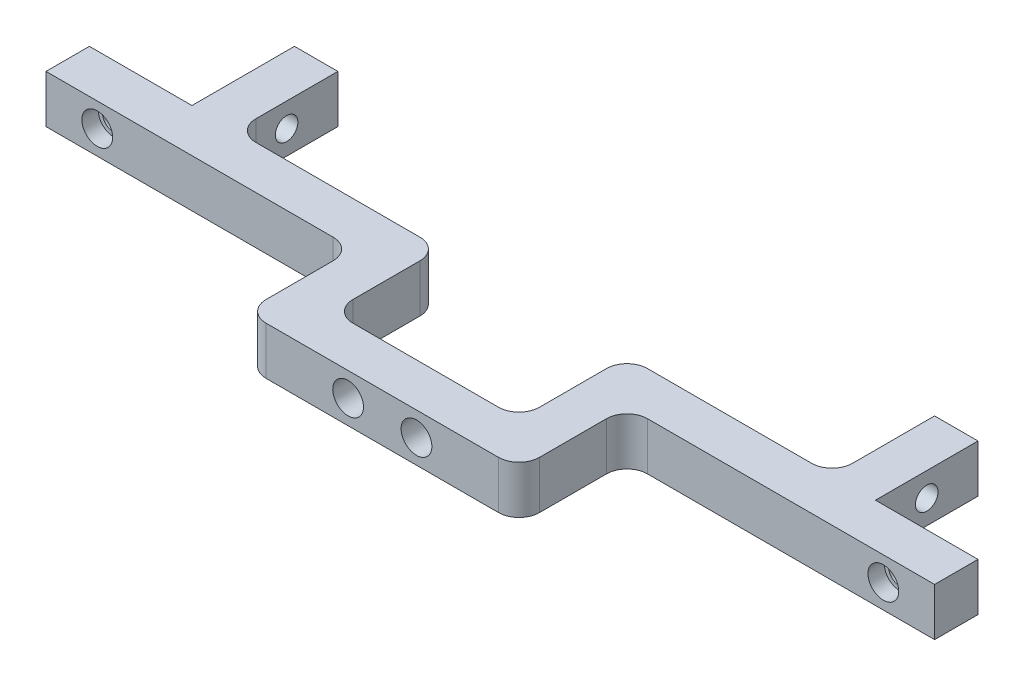
SolidWorks part; units mm, degrees
ref_plane "Front Plane" through (0, 0, 0) normal (0, 0, 1) x (1, 0, 0)
ref_plane "Top Plane" through (0, 0, 0) normal (0, 1, 0) x (1, 0, 0)
ref_plane "Right Plane" through (0, 0, 0) normal (1, 0, 0) x (0, 0, -1)
sketch "Sketch1" plane through (0, 0, 0) normal (0, 1, 0) x (1, 0, 0)
  line L1 (43.65, 15.8) -> (43.65, 30.8)
  line L2 (43.65, 30.8) -> (50, 30.8)
  line L3 (50, 30.8) -> (50, 15.8)
  line L6 (-50, 30.8) -> (-43.65, 30.8)
  line L7 (-43.65, 30.8) -> (-43.65, 15.8)
  line L9 (0, 52.9472) -> (0, -21.9318) construction
  line L10 (50, 15.8) -> (65, 15.8)
  line L13 (65, 15.8) -> (65, 9.45)
  line L15 (-65, 15.8) -> (-65, 9.45)
  line L17 (-50, 15.8) -> (-65, 15.8)
  line L18 (-50, 30.8) -> (-50, 15.8)
  line L20 (-43.65, 15.8) -> (-13.65, 15.8)
  line L22 (-13.65, 15.8) -> (-13.65, 0)
  line L23 (-13.65, 0) -> (13.65, 0)
  line L24 (13.65, 0) -> (13.65, 15.8)
  line L25 (13.65, 15.8) -> (43.65, 15.8)
  line L26 (65, 9.45) -> (20, 9.45)
  line L27 (20, 9.45) -> (20, -6.35)
  line L28 (20, -6.35) -> (-20, -6.35)
  line L29 (-20, -6.35) -> (-20, 9.45)
  line L30 (-20, 9.45) -> (-65, 9.45)
  dimension "D4" = 6.35
  dimension "D5" = 15
  dimension "D6" = 6.35
  dimension "D1" = 30
  dimension "D8" = 30
  dimension "D9" = 27.3
  dimension "D3" = 15
  dimension "D7" = 6.35
  dimension "D10" = 6.35
  dimension "D2" = 15
extrude "Boss-Extrude1" add sketch "Sketch1" along normal blind 7
sketch "Sketch2" plane through (50, 0, 0) normal (1, 0, 0) x (0, 0, -1)
  line L0 (30.8, 7) -> (30.8, 0) construction
  circle A0 centre (23.3, 3.5) radius 1.65
  dimension "D1" = 3.3
  dimension "D2" = 7.5
extrude "Cut-Extrude1" cut sketch "Sketch2" against normal through all
sketch "Sketch3" plane through (0, 0, -15.8) normal (0, 0, -1) x (-1, 0, 0)
  line L0 (-65, 3.5) -> (65, 3.5) construction
  line L3 (-65, 7) -> (-65, 0) construction
  line L4 (65, 7) -> (65, 0) construction
  circle A0 centre (-57.5, 3.5) radius 1.65
  circle A1 centre (57.5, 3.5) radius 1.65
  point P2 (0, 0)
  point P3 (0, 0)
  dimension "D2" = 3.3
  dimension "D4" = 3.3
  dimension "D1" = 7.5
  dimension "D3" = 7.5
fillet "Fillet1" radius 3 10 edges at (-43.65, 3.5, -15.8) (43.65, 3.5, -15.8) (20, 3.5, 6.35) (20, 3.5, -9.45) (-20, 3.5, -9.45) (-20, 3.5, 6.35) (13.65, 3.5, 0) (13.65, 3.5, -15.8) (-13.65, 3.5, -15.8) (-13.65, 3.5, 0)
extrude "Cut-Extrude4" cut sketch "Sketch3" against normal up to surface (6.35 mm away) up to face at (44, 3.5, -9.45)
sketch "Sketch5" plane through (0, 0, 6.35) normal (0, 0, 1) x (1, 0, 0)
  line L0 (-65, 3.5) -> (65, 3.5) construction
  line L1 (-65, 7) -> (-65, 0) construction
  line L2 (65, 7) -> (65, 0) construction
  line L3 (0, 7) -> (0, 0) construction
  line L4 (-17, 7) -> (17, 7) construction
  circle A0 centre (5, 3.5) radius 2.25
  circle A1 centre (-5, 3.5) radius 2.25
  point P13 (0, 0)
  dimension "D1" = 4.5
  dimension "D2" = 5
extrude "Cut-Extrude5" cut sketch "Sketch5" against normal up to surface (6.35 mm away) up to face at (0, 3.5, 0)
sketch "Sketch6" plane through (0, 0, -9.45) normal (0, 0, 1) x (1, 0, 0)
  circle A0 centre (-57.5, 3.5) radius 2.25
  circle A1 centre (57.5, 3.5) radius 2.25
  dimension "D1" = 4.5
extrude "Cut-Extrude6" cut sketch "Sketch6" against normal blind 2.4
equation "\"D6@Sketch1\"=\"D4@Sketch1\""
